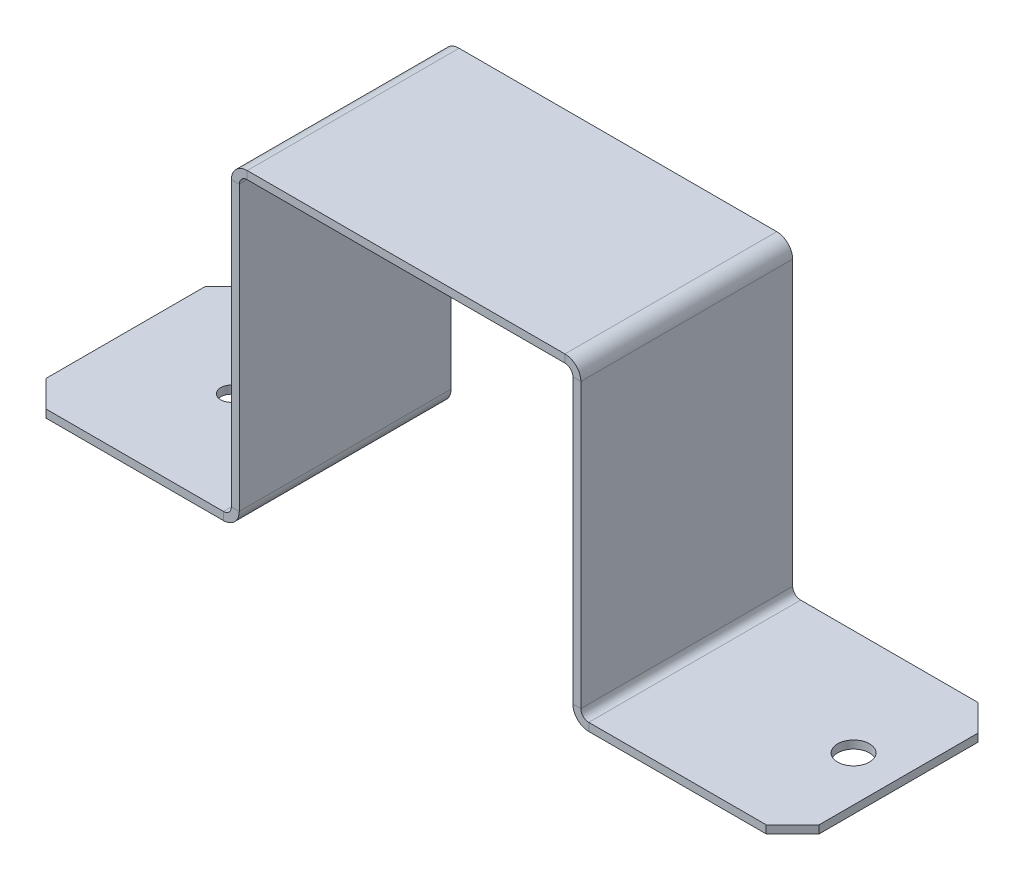
SolidWorks part; units mm, degrees
note: The reader was unsure of these and kept them because the rebuilt part matched: flange length of "Edge-Flange1", "Edge-Flange2".
ref_plane "Front Plane" through (0, 0, 0) normal (0, 0, 1) x (1, 0, 0)
ref_plane "Top Plane" through (0, 0, 0) normal (0, 1, 0) x (1, 0, 0)
ref_plane "Right Plane" through (0, 0, 0) normal (1, 0, 0) x (0, 0, -1)
sketch "Sketch1" plane through (0, 0, 0) normal (0, 1, 0) x (1, 0, 0)
  line L1 (-30, 20) -> (30, 20)
  line L2 (-30, 20) -> (-30, -20)
  line L3 (-30, -20) -> (30, -20)
  line L4 (30, 20) -> (30, -20)
  line L5 (-30, 20) -> (30, -20) construction
  line L6 (-30, -20) -> (30, 20) construction
  point P0 (0, 0)
  dimension "D1" = 60
  dimension "D2" = 40
sheet metal parameters "Sheet-Metal1" thickness 1.5 parameters "D1"=1.5
base flange "Base-Flange1" sketch "Sketch1" thickness 1.5 reverse thickness direction no parameters "D1"=1.5
edge flange "Edge-Flange1" sketch "Sketch6" flange angle 90 flange length 55 flange position bend outside bend radius 1.5 thickness 1.5 relief rectangular parameters "D6"=10
sketch "Sketch6" plane through (-30, -1.5, 0) normal (-1, 0, 0) x (0, 0, -1)
  line L0 (20, 0) -> (-20, 0) construction
  line L1 (20, 0) -> (-20, 0)
  line L2 (-20, 0) -> (-20, 55)
  line L3 (-20, 55) -> (20, 55)
  line L4 (20, 55) -> (20, 0)
bend "EdgeBend1" bend radius 1.5 bend angle 90 parameters "D5"=1
edge flange "Edge-Flange2" sketch "Sketch9" flange angle 90 flange length 40 flange position bend outside bend radius 1.5 thickness 1.5 relief rectangular parameters "D6"=10
sketch "Sketch9" plane through (-33, -56.5, 0) normal (0, -1, 0) x (0, 0, 1)
  line L2 (-20, 0) -> (-20, 40)
  line L3 (-20, 40) -> (20, 40)
  line L4 (20, 40) -> (20, 0)
  line L5 (-20, 0) -> (20, 0) construction
  line L6 (-20, 0) -> (20, 0)
bend "EdgeBend2" bend radius 1.5 bend angle 90 parameters "D5"=2
ref_plane "Plane1" through (0, 0, 0) normal (1, 0, 0) x (0, 0, -1)
mirror "Mirror1" about plane through (0, 0, 0) normal (1, 0, 0) of "Edge-Flange2", "Edge-Flange1"
bend "MirrorBend1" bend radius 1.5 bend angle 90 parameters "D5"=3
bend "MirrorBend2" bend radius 1.5 bend angle 90 parameters "D5"=4
chamfer "Chamfer1" distance 5 angle 45 4 edges at (73, -58.75, -20) (73, -58.75, 20) (-73, -58.75, -20) (-73, -58.75, 20)
sketch "Sketch10" plane through (0, -58, 0) normal (0, 1, 0) x (1, 0, 0)
  line L0 (-73, -15) -> (-73, 15) construction
  line L1 (73, -15) -> (73, 15) construction
  circle A0 centre (-53, 0) radius 2
  circle A1 centre (64.5, 0) radius 3
  dimension "D1" = 4
  dimension "D2" = 20
  dimension "D3" = 6
  dimension "D4" = 8.5
extrude "Cut-Extrude1" cut sketch "Sketch10" against normal up to next normal cut yes
flat pattern "Flat-Pattern1" [suppressed]
sketch "Bend-Lines1" plane through (0, 0, 0) normal (0, 1, 0) x (1, 0, 0)
sketch3d "Bounding-Box1" [suppressed]
  line L0 (-30, -20, 0) -> (30, -20, 0) construction
  line L1 (-30, 20, 0) -> (30, 20, 0) construction
  line L2 (-30, -20, 0) -> (-30, 20, 0) construction
  line L3 (30, -20, 0) -> (30, 20, 0) construction
bend of the flat pattern "Flatten-<EdgeBend1>1"
bend of the flat pattern "Flatten-<EdgeBend2>1"
bend of the flat pattern "Flatten-<MirrorBend1>1"
bend of the flat pattern "Flatten-<MirrorBend2>1"
